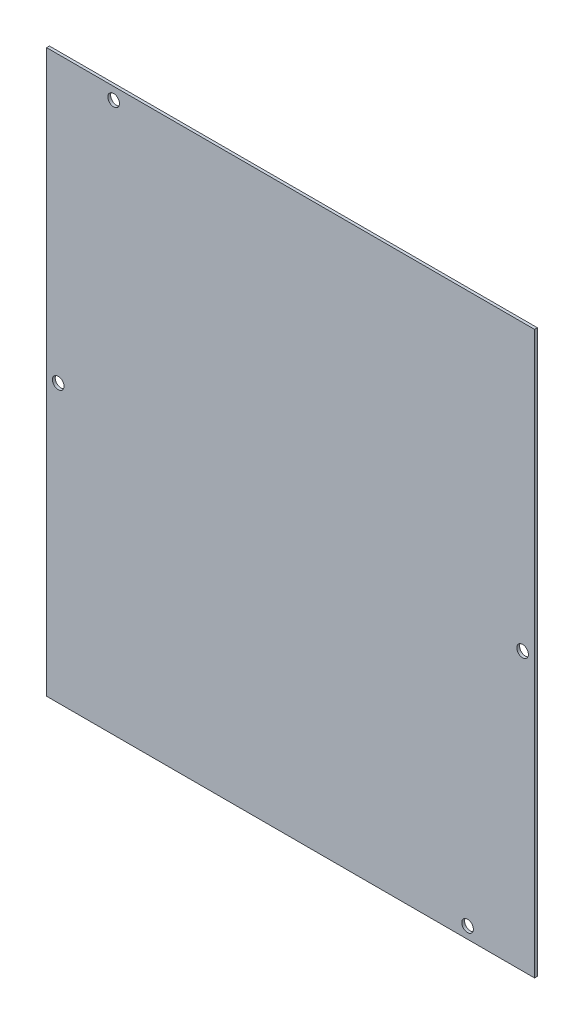
SolidWorks part; units mm, degrees
ref_plane "Alzado" through (0, 0, 0) normal (0, 0, 1) x (1, 0, 0)
ref_plane "Planta" through (0, 0, 0) normal (0, 1, 0) x (1, 0, 0)
ref_plane "Vista lateral" through (0, 0, 0) normal (1, 0, 0) x (0, 0, -1)
sketch "Croquis1" plane through (0, 0, 0) normal (0, 0, 1) x (1, 0, 0)
  line L1 (-165.481, -190.5) -> (165.481, -190.5)
  line L2 (-165.481, -190.5) -> (-165.481, 190.5)
  line L3 (-165.481, 190.5) -> (165.481, 190.5)
  line L4 (165.481, -190.5) -> (165.481, 190.5)
  line L5 (-165.481, -190.5) -> (165.481, 190.5) construction
  line L6 (-165.481, 190.5) -> (165.481, -190.5) construction
  point P0 (0, 0)
  dimension "D1" = 381
  dimension "D2" = 330.962
base flange "Brida base1" sketch "Croquis1" thickness 1.905 reverse thickness direction no parameters "D1"=1.905
sketch "Croquis6" plane through (0, 0, 0) normal (0, 0, 1) x (1, 0, 0)
  line L0 (-165.481, -190.5) -> (165.481, -190.5) construction
  line L1 (-165.481, 190.5) -> (-165.481, -190.5) construction
  circle A0 centre (-120.015, 182.372) radius 3.937
  circle A1 centre (-157.607, -2.54) radius 3.937
  circle A2 centre (157.353, -2.54) radius 3.937
  circle A3 centre (120.015, -182.626) radius 3.937
  dimension "D8" = 7.874
  dimension "D1" = 7.874
  dimension "D2" = 285.496
  dimension "D3" = 187.96
  dimension "D4" = 7.874
  dimension "D5" = 322.834
  dimension "D6" = 372.872
  dimension "D7" = 45.466
extrude "Cortar-Extruir1" cut sketch "Croquis6" against normal through all normal cut yes
sketch "Líneas de pliegue1" [suppressed] plane through (0, 0, 0) normal (0, 1, 0) x (1, 0, 0)
sketch "Cuadro delimitador1" [suppressed] plane through (0, 0, 0) normal (0, 1, 0) x (1, 0, 0)
sheet metal parameters "Chapa metálica1" thickness 1.905 parameters "D1"=1.905
flat pattern "Chapa desplegada1" [suppressed]
sketch "Líneas de pliegue2" plane through (0, 0, 0) normal (0, 1, 0) x (1, 0, 0)
sketch3d "Cuadro delimitador2" [suppressed]
  line L0 (-165.481, 190.5, 0) -> (-165.481, -190.5, 0) construction
  line L1 (165.481, 190.5, 0) -> (165.481, -190.5, 0) construction
  line L2 (-165.481, 190.5, 0) -> (165.481, 190.5, 0) construction
  line L3 (-165.481, -190.5, 0) -> (165.481, -190.5, 0) construction
sheet metal parameters "Chapa metálica2" thickness 1.905 parameters "D1"=1.905
flat pattern "Chapa desplegada1"
sketch "Líneas de pliegue2" plane through (0, 0, 0) normal (0, 1, 0) x (1, 0, 0)
sketch3d "Cuadro delimitador2" [suppressed]
  line L0 (165.481, 190.5, 0) -> (165.481, -190.5, 0) construction
  line L1 (-165.481, 190.5, 0) -> (-165.481, -190.5, 0) construction
  line L2 (165.481, 190.5, 0) -> (-165.481, 190.5, 0) construction
  line L3 (165.481, -190.5, 0) -> (-165.481, -190.5, 0) construction
